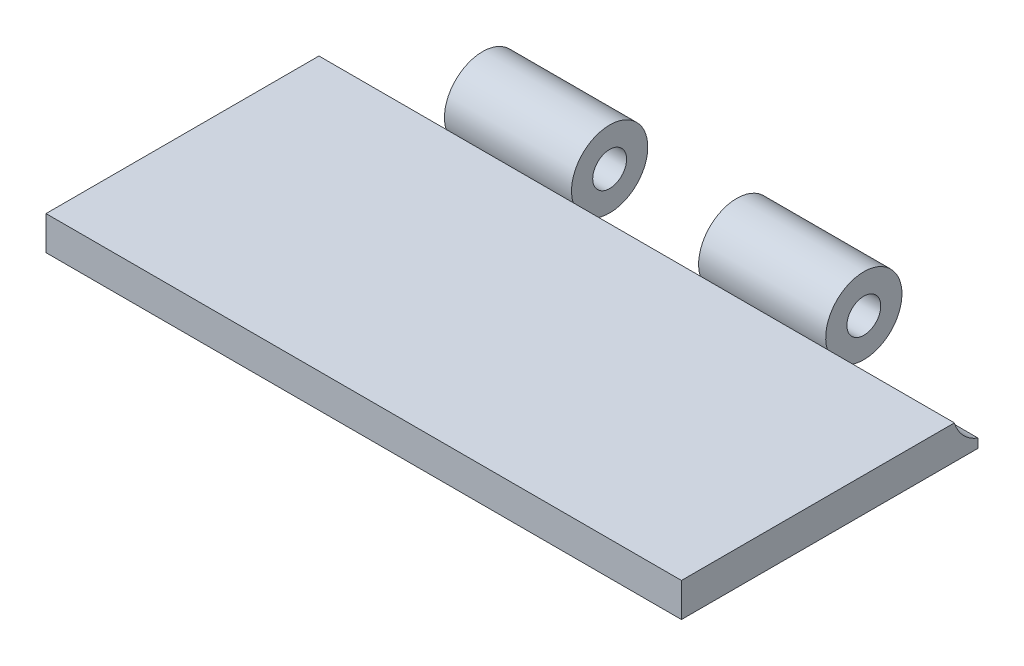
SolidWorks part; units mm, degrees
ref_plane "Front Plane" through (0, 0, 0) normal (0, 0, 1) x (1, 0, 0)
ref_plane "Top Plane" through (0, 0, 0) normal (0, 1, 0) x (1, 0, 0)
ref_plane "Right Plane" through (0, 0, 0) normal (1, 0, 0) x (0, 0, -1)
sketch "Sketch1" plane through (0, 0, 0) normal (0, 1, 0) x (1, 0, 0)
  line L1 (-101.1962, 19.5813) -> (48.8038, 19.5813)
  line L2 (-101.1962, 19.5813) -> (-101.1962, -50.4187)
  line L3 (-101.1962, -50.4187) -> (48.8038, -50.4187)
  line L4 (48.8038, 19.5813) -> (48.8038, -50.4187)
  line L5 (-101.1962, 19.5813) -> (48.8038, -50.4187) construction
  line L6 (-101.1962, -50.4187) -> (48.8038, 19.5813) construction
  point P0 (-26.1962, -15.4187)
  dimension "D1" = 150
  dimension "D2" = 70
extrude "Boss-Extrude1" add sketch "Sketch1" along normal blind 8
ref_plane "Plane1" through (-101.1962, 0, 0) normal (-1, 0, 0) x (0, 0, 1)
sketch "Sketch2" plane through (-101.1962, 0, 0) normal (-1, 0, 0) x (0, 0, 1)
  line L0 (-19.5813, 8) -> (-22.631, 10.5883)
  circle A0 centre (-22.631, 10.5883) radius 4
  circle A1 centre (-22.631, 10.5883) radius 9
ref_plane "Plane2" through (0, 4, 0) normal (0, -1, 0) x (-1, 0, 0)
sketch "Sketch4" plane through (-101.1962, 0, 0) normal (-1, 0, 0) x (0, 0, 1)
extrude "Boss-Extrude3" add sketch "Sketch2" against normal blind 30 from offset 30 contours A1 A0 region at (-101.1962, 10.5883, -31.3765) offset against normal yes
pattern_linear "LPattern2" count 2 spacing 60 along (1, 0, 0) of "Boss-Extrude3"
ref_plane "Plane3" through (-71.1962, 0, 0) normal (-1, 0, 0) x (0, 0, 1)
sketch "Sketch5" plane through (-71.1962, 0, 0) normal (-1, 0, 0) x (0, 0, 1)
  circle A0 centre (-22.631, 10.5883) radius 9
extrude "Cut-Extrude1" cut sketch "Sketch5" along normal blind 30
sketch "Sketch6" plane through (-71.1962, 0, 0) normal (-1, 0, 0) x (0, 0, 1)
  circle A0 centre (-22.631, 10.5883) radius 9
extrude "Cut-Extrude2" cut sketch "Sketch6" against normal blind 30 from offset 30 offset against normal yes
sketch "Sketch7" plane through (-71.1962, 0, 0) normal (-1, 0, 0) x (0, 0, 1)
  circle A0 centre (-22.631, 10.5883) radius 9
extrude "Cut-Extrude3" cut sketch "Sketch7" against normal blind 30 from offset 90 offset against normal yes
scale "Scale1" scale about centroid uniform scaling yes scale factor 0.333333
